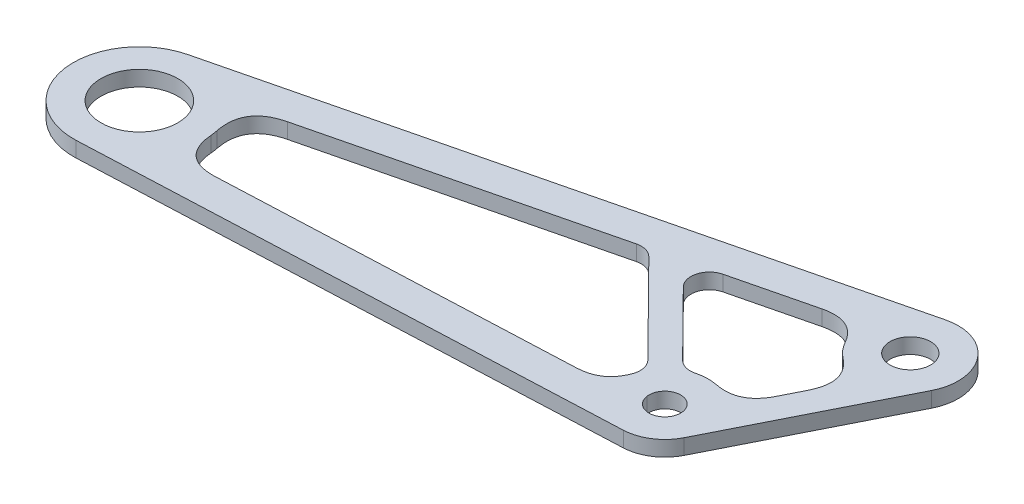
SolidWorks part; units mm, degrees
material "6061-T6 (SS)"
ref_plane "Front Plane" through (0, 0, 0) normal (0, 0, 1) x (1, 0, 0)
ref_plane "Top Plane" through (0, 0, 0) normal (0, 1, 0) x (1, 0, 0)
ref_plane "Right Plane" through (0, 0, 0) normal (1, 0, 0) x (0, 0, -1)
sketch "Sketch1" plane through (0, 0, 0) normal (0, 1, 0) x (1, 0, 0)
  line L0 (0, 0) -> (124.8778, 34.4406) construction
  line L1 (124.8778, 34.4406) -> (108.585, 0) construction
  line L2 (108.585, 0) -> (0, 0) construction
  line L3 (-3.2476, 13.2606) -> (122.5214, 44.0623)
  line L5 (116.6057, -4.036) -> (133.7266, 29.9879)
  line L6 (108.585, 0) -> (109.8191, -8.8937) construction
  line L7 (-1.8881, 7.7097) -> (123.8808, 38.5113)
  line L8 (111.5006, -1.4671) -> (128.6215, 32.5568)
  line L9 (0.3416, -7.9301) -> (108.7255, -3.2609)
  line L10 (108.585, 0) -> (80.9067, 27.9867) construction
  line L11 (108.585, 0) -> (108.585, 29.9472) construction
  line L12 (74.1927, 26.3424) -> (50.6623, -5.7623) construction
  line L13 (78.0308, 27.2823) -> (53.9142, -5.6222)
  line L14 (70.3546, 25.4024) -> (47.4105, -5.9024)
  line L15 (78.0308, 27.2823) -> (100.7231, 4.3373)
  line L16 (83.7825, 28.691) -> (104.3351, 7.9094)
  line L17 (62.4275, 10.29) -> (60.3789, 11.7916) construction
  line L18 (62.4275, 10.29) -> (64.4762, 8.7885) construction
  line L19 (94.7458, 13.9933) -> (92.9399, 12.2073) construction
  line L20 (94.7458, 13.9933) -> (96.5518, 15.7794) construction
  line L21 (114.3014, 6.9241) -> (123.2323, 24.6722)
  line L22 (0.5876, -13.6398) -> (108.9715, -8.9706)
  line L23 (9.9856, 9.3101) -> (114.9891, 35.0261)
  line L24 (12.1896, -6.1485) -> (99.9242, -2.3689)
  circle A0 centre (0, 0) radius 7.9375
  circle A1 centre (124.8778, 34.4406) radius 4.191
  circle A2 centre (108.585, 0) radius 3.2639
  circle A3 centre (0, 0) radius 13.6525
  circle A4 centre (108.585, 0) radius 8.9789
  circle A5 centre (124.8778, 34.4406) radius 9.906
  arc A6 (-3.2476, 13.2606) -> (6.5337, -11.9876) centre (0, 0) ccw
  arc A7 (116.6057, -4.036) -> (108.585, -8.9789) centre (108.585, 0) cw
  arc A8 (122.5214, 44.0623) -> (133.7266, 29.9879) centre (124.8778, 34.4406) cw
  dimension "D4" = 15.875
  dimension "D5" = 6.5278
  dimension "D6" = 8.382
  dimension "D7" = 5.715
  dimension "D8" = 5.715
  dimension "D9" = 5.715
  dimension "D1" = 129.54
  dimension "D2" = 38.1
  dimension "D3" = 108.585
  dimension "D10" = 97.9
  dimension "D11" = 70
  dimension "D12" = 40
  dimension "D13" = 5.08
  dimension "D14" = 1.27
  dimension "D15" = 1.27
  dimension "D16" = 1.27
extrude "Boss-Extrude4" add sketch "Sketch1" against normal blind 3.175 contours A5 L7 A1 L8 | A5 L3 A3 L7 | A3 L9 A0 L7 | L9 A3 L7 A0 | A3 L23 L14 L7 | A3 L9 L14 L24 | A4 L9 A3 L22 | A4 L24 L13 L9 | L24 L14 L9 L13 | A4 L16 L23 L15 | L14 L23 L13 L7 | L15 L23 L16 L7 | A5 L7 L16 L23 | L13 L23 L15 | A5 L8 A4 L5 | L7 A5 L8 A1 | A4 L8 A2 L9 | L8 A4 L9 A2
ref_plane "Plane1" through (108.585, 0, 0) normal (0.1374, 0, 0.9905) x (0.9905, 0, -0.1374)
split line "Split Line1"
sketch "Sketch2" [suppressed] plane through (0, -3.175, 0) normal (0, -1, 0) x (1, 0, 0)
  line L1 (69.4473, -23.6659) -> (60.7288, -1.2641)
  line L2 (62.8949, 2.1892) -> (101.6127, 5.2609)
  line L3 (101.2476, -37.8411) -> (79.7056, -31.0891)
  line L4 (79.2148, -26.4545) -> (98.3531, -15.6299)
  line L5 (59.9072, -25.992) -> (7.538, -8.592)
  line L6 (63.0965, -22.7173) -> (54.4829, 1.0899)
  line L7 (51.7805, 2.7463) -> (11.1946, -2.3078)
  line L8 (73.1912, -24.8791) -> (102.155, -6.1958)
  line L9 (104.5239, -35.0732) -> (102.1201, -17.4966)
  circle A0 centre (111.76, 0) radius 11.43 construction
  circle A3 centre (0, 0) radius 11.43 construction
  arc A4 (11.1946, -2.3078) -> (7.538, -8.592) centre (0, 0) cw
  arc A5 (101.6127, 5.2609) -> (102.155, -6.1958) centre (111.76, 0) ccw
  arc A6 (101.2476, -37.8411) -> (104.5239, -35.0732) centre (102.0073, -35.4173) ccw
  arc A7 (98.3531, -15.6299) -> (102.1201, -17.4966) centre (99.6035, -17.8407) cw
  arc A8 (69.4473, -23.6659) -> (73.1912, -24.8791) centre (71.8144, -22.7446) ccw
  arc A9 (60.7288, -1.2641) -> (62.8949, 2.1892) centre (63.0958, -0.3428) cw
  arc A10 (63.0965, -22.7173) -> (59.9072, -25.992) centre (60.7081, -23.5815) cw
  arc A11 (54.4829, 1.0899) -> (51.7805, 2.7463) centre (52.0944, 0.2257) ccw
  arc A12 (79.2148, -26.4545) -> (79.7056, -31.0891) centre (80.4653, -28.6654) ccw
  dimension "D1" = 2.54
  dimension "D2" = 2.54
  dimension "D3" = 2.54
  dimension "D4" = 2.54
  dimension "D5" = 2.54
  dimension "D6" = 2.54
  dimension "D7" = 2.54
extrude "Cut-Extrude2" [suppressed] cut sketch "Sketch2" against normal through all
fillet "Fillet1" radius 7.62 6 edges at (115.2605, -1.5875, -6.0049) (124.5869, -1.5875, -24.5389) (114.9891, -1.5875, -35.0261) (9.9856, -1.5875, -9.3101) (99.9242, -1.5875, 2.3689) (12.1896, -1.5875, 6.1485) conic rho 0.5
fillet "Fillet2" radius 3.81 4 edges at (104.3351, -1.5875, -7.9094) (100.7231, -1.5875, -4.3373) (84.8235, -1.5875, -27.6384) (79.0718, -1.5875, -26.2298)
fillet "Fillet3" [suppressed] radius 2.54
equation "\"x\"= .05"
